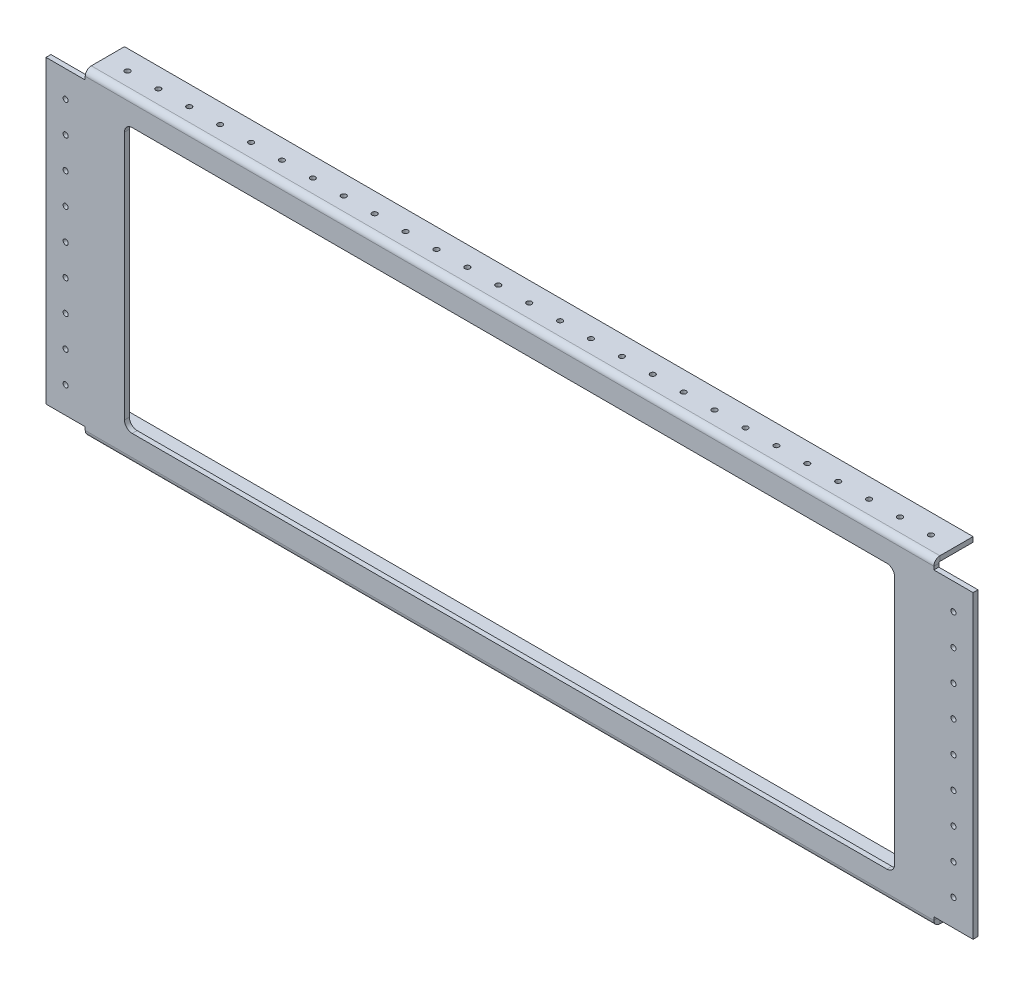
SolidWorks part; units mm, degrees
note: The reader was unsure of these and kept them because the rebuilt part matched: thickness of "Base-Flange1", "Edge-Flange1", "Sheet-Metal1", "Sheet-Metal2", "Sheet-Metal3", "Sheet-Metal4", "Sheet-Metal5", "Sheet-Metal6"; flange length of "Edge-Flange1".
ref_plane "Front Plane" through (0, 0, 0) normal (0, 0, 1) x (1, 0, 0)
ref_plane "Top Plane" through (0, 0, 0) normal (0, 1, 0) x (1, 0, 0)
ref_plane "Right Plane" through (0, 0, 0) normal (1, 0, 0) x (0, 0, -1)
sketch "Sketch1" plane through (0, 0, 0) normal (0, 0, 1) x (1, 0, 0)
  line L1 (-300, 103.175) -> (300, 103.175)
  line L2 (-300, 103.175) -> (-300, -103.175)
  line L3 (-300, -103.175) -> (300, -103.175)
  line L4 (300, 103.175) -> (300, -103.175)
  line L5 (-300, 103.175) -> (300, -103.175) construction
  line L6 (-300, -103.175) -> (300, 103.175) construction
  point P0 (0, 0)
  dimension "D1" = 600
  dimension "D2" = 206.35
base flange "Base-Flange1" sketch "Sketch1" thickness 3.18 reverse thickness direction no parameters "D1"=0.7366
sketch "Sketch6" plane through (0, 0, 0) normal (0, 0, 1) x (1, 0, 0)
  line L1 (-300, 103.175) -> (-274.6, 103.175)
  line L2 (-300, 103.175) -> (-300, 97.175)
  line L3 (-300, 97.175) -> (-274.6, 97.175)
  line L4 (-274.6, 103.175) -> (-274.6, 97.175)
  line L5 (-300, -103.175) -> (-274.6, -103.175)
  line L6 (-300, -103.175) -> (-300, -97.175)
  line L7 (-300, -97.175) -> (-274.6, -97.175)
  line L8 (-274.6, -103.175) -> (-274.6, -97.175)
  line L9 (300, -103.175) -> (274.6, -103.175)
  line L10 (300, -103.175) -> (300, -97.175)
  line L11 (300, -97.175) -> (274.6, -97.175)
  line L12 (274.6, -103.175) -> (274.6, -97.175)
  line L13 (300, 103.175) -> (274.6, 103.175)
  line L14 (300, 103.175) -> (300, 97.175)
  line L15 (300, 97.175) -> (274.6, 97.175)
  line L16 (274.6, 103.175) -> (274.6, 97.175)
  dimension "D1" = 25.4
  dimension "D2" = 6
extrude "Cut-Extrude1" cut sketch "Sketch6" against normal blind 10 normal cut yes
edge flange "Edge-Flange1" sketch "Sketch13" flange profiles "Sketch13", "Sketch14" flange angle 90 flange length 25.4 flange position material inside bend radius 0.7366 thickness 3.18 relief rectangular parameters "D6"=10, "D8"=1
sketch "Sketch13" plane through (0, 103.175, -3.18) normal (0, -1, 0) x (-1, 0, 0)
  line L0 (274.6, 0) -> (-274.6, 0) construction
  line L1 (274.6, 0) -> (-274.6, 0)
  line L2 (274.6, 0) -> (274.6, 22.22)
  line L3 (274.6, 22.22) -> (-274.6, 22.22)
  line L4 (-274.6, 22.22) -> (-274.6, 0)
sketch "Sketch14" plane through (0, -103.175, -3.18) normal (0, 1, 0) x (1, 0, 0)
  line L0 (274.6, 0) -> (-274.6, 0) construction
  line L1 (274.6, 0) -> (-274.6, 0)
  line L2 (274.6, 0) -> (274.6, 22.22)
  line L3 (274.6, 22.22) -> (-274.6, 22.22)
  line L4 (-274.6, 22.22) -> (-274.6, 0)
bend "EdgeBend1" bend radius 0.7366 bend angle 90 parameters "D5"=1
bend "EdgeBend2" bend radius 0.7366 bend angle 90 parameters "D5"=2
sketch "Sketch15" plane through (0, 0, 0) normal (0, 0, 1) x (1, 0, 0)
  line L0 (-300, 103.175) -> (300, -103.175) construction
  line L1 (-249.2, 85.704) -> (249.2, 85.704)
  line L2 (-249.2, 85.704) -> (-249.2, -85.704)
  line L3 (-249.2, -85.704) -> (249.2, -85.704)
  line L4 (249.2, 85.704) -> (249.2, -85.704)
  line L5 (-249.2, 85.704) -> (249.2, -85.704) construction
  line L6 (-249.2, -85.704) -> (249.2, 85.704) construction
  line L7 (-300, 97.175) -> (-300, -97.175) construction
  line L8 (-274.6, 103.175) -> (274.6, 103.175) construction
  point P0 (0, 0)
  dimension "D1" = 50.8
  dimension "D2" = 17.471
extrude "Cut-Extrude2" cut sketch "Sketch15" against normal blind 10 normal cut yes
fillet "Fillet1" radius 5 4 edges at (-249.2, -85.704, -1.59) (249.2, -85.704, -1.59) (249.2, 85.704, -1.59) (-249.2, 85.704, -1.59)
sketch "Sketch16" plane through (0, 0, 0) normal (0, 0, 1) x (1, 0, 0)
  line L0 (-300, 97.175) -> (-300, -97.175) construction
  line L1 (-287.3, 0) -> (0, 0) construction
  line L2 (0, -13.97) -> (0, 13.97) construction
  circle A0 centre (-287.3, 0) radius 1.65
  circle A1 centre (-287.3, 20) radius 1.65
  circle A2 centre (-287.3, 40) radius 1.65
  circle A3 centre (-287.3, 60) radius 1.65
  circle A4 centre (-287.3, -20) radius 1.65
  circle A5 centre (-287.3, -40) radius 1.65
  circle A6 centre (-287.3, -60) radius 1.65
  circle A7 centre (287.3, -60) radius 1.65
  circle A8 centre (287.3, -40) radius 1.65
  circle A9 centre (287.3, -20) radius 1.65
  circle A10 centre (287.3, 0) radius 1.65
  circle A11 centre (287.3, 20) radius 1.65
  circle A12 centre (287.3, 40) radius 1.65
  circle A13 centre (287.3, 60) radius 1.65
  circle A14 centre (-287.3, 80) radius 1.65
  circle A15 centre (-287.3, -80) radius 1.65
  circle A16 centre (287.3, -80) radius 1.65
  circle A17 centre (287.3, 80) radius 1.65
  dimension "D1" = 3.3
  dimension "D5" = 20
  dimension "D2" = 12.7
  dimension "D6" = 20
  dimension "D3" = 5
  dimension "D4" = 5
extrude "Cut-Extrude3" cut sketch "Sketch16" against normal blind 10 normal cut yes
sketch "Sketch17" plane through (0, 103.175, 0) normal (0, 1, 0) x (1, 0, 0)
  line L0 (0, 0) -> (0, 25.4) construction
  line L1 (274.6, 0) -> (-274.6, 0) construction
  line L2 (-274.6, 25.4) -> (274.6, 25.4) construction
  circle A0 centre (0, 12.7) radius 1.65
  circle A1 centre (20, 12.7) radius 1.65
  circle A2 centre (40, 12.7) radius 1.65
  circle A3 centre (60, 12.7) radius 1.65
  circle A4 centre (80, 12.7) radius 1.65
  circle A5 centre (100, 12.7) radius 1.65
  circle A6 centre (120, 12.7) radius 1.65
  circle A7 centre (140, 12.7) radius 1.65
  circle A8 centre (160, 12.7) radius 1.65
  circle A9 centre (180, 12.7) radius 1.65
  circle A10 centre (200, 12.7) radius 1.65
  circle A11 centre (220, 12.7) radius 1.65
  circle A12 centre (240, 12.7) radius 1.65
  circle A13 centre (260, 12.7) radius 1.65
  circle A14 centre (-20, 12.7) radius 1.65
  circle A15 centre (-40, 12.7) radius 1.65
  circle A16 centre (-60, 12.7) radius 1.65
  circle A17 centre (-80, 12.7) radius 1.65
  circle A18 centre (-100, 12.7) radius 1.65
  circle A19 centre (-120, 12.7) radius 1.65
  circle A20 centre (-140, 12.7) radius 1.65
  circle A21 centre (-160, 12.7) radius 1.65
  circle A22 centre (-180, 12.7) radius 1.65
  circle A23 centre (-200, 12.7) radius 1.65
  circle A24 centre (-220, 12.7) radius 1.65
  circle A25 centre (-240, 12.7) radius 1.65
  circle A26 centre (-260, 12.7) radius 1.65
  dimension "D1" = 3.3
  dimension "D2" = 12.7
  dimension "D4" = 20
  dimension "D6" = 20
  dimension "D3" = 14
  dimension "D5" = 14
extrude "Cut-Extrude4" cut sketch "Sketch17" against normal through all normal cut yes
sketch "Bend-Lines1" [suppressed] plane through (0, 0, 0) normal (0, 1, 0) x (1, 0, 0)
sketch "Bounding-Box1" [suppressed] plane through (0, 0, 0) normal (0, 1, 0) x (1, 0, 0)
sheet metal parameters "Sheet-Metal1" thickness 3.18 parameters "D1"=0.7366, "D7"=8
flat pattern "Flat-Pattern1" [suppressed]
sketch "Bend-Lines2" plane through (0, 0, 0) normal (0, 1, 0) x (1, 0, 0)
sketch3d "Bounding-Box2" [suppressed]
  line L0 (350, -150, 0) -> (-350, -150, 0) construction
  line L1 (350, 150, 0) -> (-350, 150, 0) construction
  line L2 (350, -150, 0) -> (350, 150, 0) construction
  line L3 (-350, -150, 0) -> (-350, 150, 0) construction
sheet metal parameters "Sheet-Metal2" thickness 3.18 parameters "D1"=0.7366, "D7"=8
flat pattern "Flat-Pattern1"
sketch "Bend-Lines2" plane through (0, 0, 0) normal (0, 1, 0) x (1, 0, 0)
sketch3d "Bounding-Box2" [suppressed]
  line L0 (-350, -150, 0) -> (350, -150, 0) construction
  line L1 (-350, 150, 0) -> (350, 150, 0) construction
  line L2 (-350, -150, 0) -> (-350, 150, 0) construction
  line L3 (350, -150, 0) -> (350, 150, 0) construction
sheet metal parameters "Sheet-Metal3" thickness 3.18 parameters "D1"=0.7366, "D7"=8
flat pattern "Flat-Pattern1"
sketch "Bend-Lines2" plane through (0, 0, 0) normal (0, 0, 1) x (1, 0, 0)
  line L0 (-324.6, -144.9835) -> (324.6, -144.9835) construction
  line L1 (324.6, 144.9835) -> (-324.6, 144.9835) construction
  line L2 (-324.6, -144.9835) -> (324.6, -144.9835) construction
  line L3 (324.6, 144.9835) -> (-324.6, 144.9835) construction
sketch3d "Bounding-Box2" [suppressed]
  line L0 (-350, -165.367, 0) -> (350, -165.367, 0) construction
  line L1 (-350, 165.367, 0) -> (350, 165.367, 0) construction
  line L2 (-350, -165.367, 0) -> (-350, 165.367, 0) construction
  line L3 (350, -165.367, 0) -> (350, 165.367, 0) construction
bend of the flat pattern "Flatten-<EdgeBend1>1"
bend of the flat pattern "Flatten-<EdgeBend2>1"
sheet metal parameters "Sheet-Metal4" thickness 3.18 parameters "D1"=0.7366, "D7"=8
flat pattern "Flat-Pattern1"
sketch "Bend-Lines2" plane through (0, 0, 0) normal (0, 0, 1) x (1, 0, 0)
  line L0 (-274.6, -101.0857) -> (274.6, -101.0857) construction
  line L1 (274.6, 101.0857) -> (-274.6, 101.0857) construction
  line L2 (-274.6, -101.0857) -> (274.6, -101.0857) construction
  line L3 (274.6, 101.0857) -> (-274.6, 101.0857) construction
sketch3d "Bounding-Box2" [suppressed]
  line L0 (-300, -124.3964, 0) -> (300, -124.3964, 0) construction
  line L1 (-300, 124.3964, 0) -> (300, 124.3964, 0) construction
  line L2 (-300, -124.3964, 0) -> (-300, 124.3964, 0) construction
  line L3 (300, -124.3964, 0) -> (300, 124.3964, 0) construction
bend of the flat pattern "Flatten-<EdgeBend1>1"
bend of the flat pattern "Flatten-<EdgeBend2>1"
sheet metal parameters "Sheet-Metal5" thickness 3.18 parameters "D1"=0.7366, "D7"=8
flat pattern "Flat-Pattern1"
sketch "Bend-Lines2" plane through (0, 0, 0) normal (0, 0, 1) x (1, 0, 0)
  line L0 (-274.6, -101.0857) -> (274.6, -101.0857) construction
  line L1 (274.6, 101.0857) -> (-274.6, 101.0857) construction
  line L2 (-274.6, -101.0857) -> (274.6, -101.0857) construction
  line L3 (274.6, 101.0857) -> (-274.6, 101.0857) construction
sketch3d "Bounding-Box2" [suppressed]
  line L0 (-300, -124.3964, 0) -> (300, -124.3964, 0) construction
  line L1 (-300, 124.3964, 0) -> (300, 124.3964, 0) construction
  line L2 (-300, -124.3964, 0) -> (-300, 124.3964, 0) construction
  line L3 (300, -124.3964, 0) -> (300, 124.3964, 0) construction
bend of the flat pattern "Flatten-<EdgeBend1>1"
bend of the flat pattern "Flatten-<EdgeBend2>1"
sheet metal parameters "Sheet-Metal6" thickness 3.18 parameters "D1"=0.7366, "D7"=8
flat pattern "Flat-Pattern1"
sketch "Bend-Lines2" plane through (0, 0, 0) normal (0, 0, 1) x (1, 0, 0)
  line L0 (-274.6, -101.0857) -> (274.6, -101.0857) construction
  line L1 (274.6, 101.0857) -> (-274.6, 101.0857) construction
  line L2 (-274.6, -101.0857) -> (274.6, -101.0857) construction
  line L3 (274.6, 101.0857) -> (-274.6, 101.0857) construction
sketch3d "Bounding-Box2" [suppressed]
  line L0 (-300, -124.3964, 0) -> (300, -124.3964, 0) construction
  line L1 (-300, 124.3964, 0) -> (300, 124.3964, 0) construction
  line L2 (-300, -124.3964, 0) -> (-300, 124.3964, 0) construction
  line L3 (300, -124.3964, 0) -> (300, 124.3964, 0) construction
bend of the flat pattern "Flatten-<EdgeBend1>1"
bend of the flat pattern "Flatten-<EdgeBend2>1"
